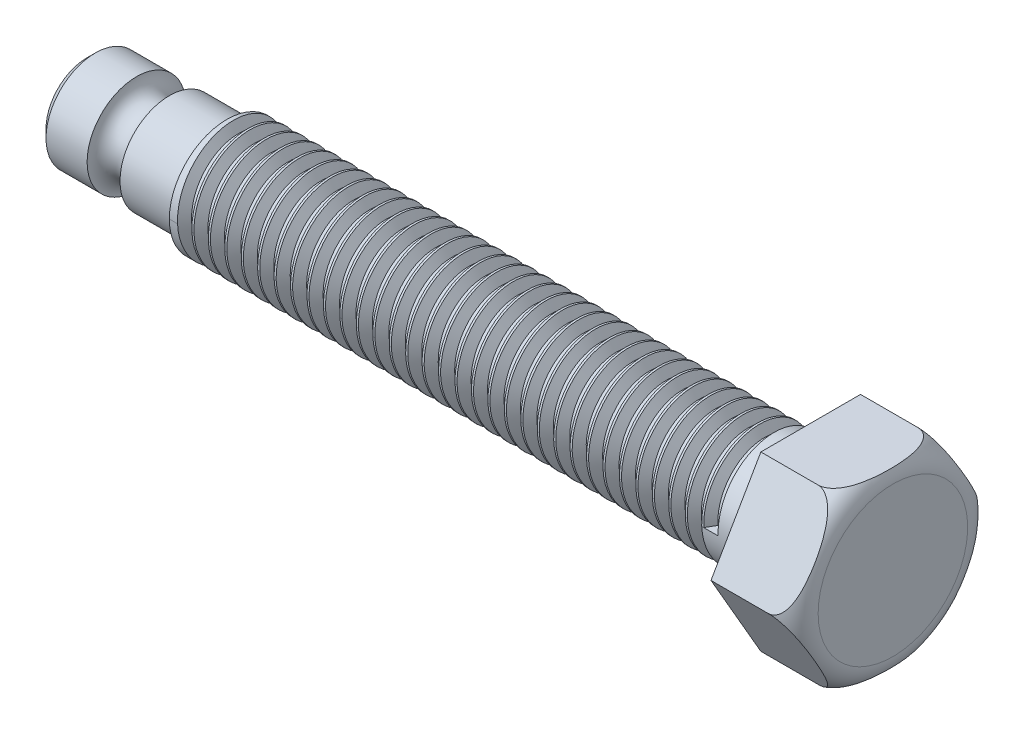
SolidWorks part; units mm, degrees
ref_plane "Front Plane" through (0, 0, 0) normal (0, 0, 1) x (1, 0, 0)
ref_plane "Top Plane" through (0, 0, 0) normal (0, 1, 0) x (1, 0, 0)
ref_plane "Right Plane" through (0, 0, 0) normal (1, 0, 0) x (0, 0, -1)
sketch "Esquisse1" plane through (0, 0, 0) normal (0, 0, 1) x (1, 0, 0)
  line L0 (-21.5385, 0) -> (27.7846, 0) construction
  line L1 (0, 21) -> (0, -25.0923) construction
  line L2 (0, 0) -> (0, 6)
  line L3 (0, 6) -> (6, 6)
  line L4 (88, 6) -> (88, 14)
  line L5 (88, 14) -> (98, 14)
  line L6 (98, 14) -> (98, 0)
  line L7 (98, 0) -> (0, 0)
  line L8 (10, 6) -> (17, 6)
  line L9 (17, 6) -> (17, 7)
  line L10 (17, 7) -> (88, 7)
  arc A0 (6, 6) -> (10, 6) centre (8, 6) ccw
  dimension "D3" = 2
  dimension "D1" = 6
  dimension "D2" = 8
  dimension "D4" = 10
  dimension "D5" = 14
  dimension "D6" = 80
  dimension "D7" = 17
  dimension "D8" = 1
revolve "Révolution2" add sketch "Esquisse1" angle 360 about L0 region at (54.4948, 4.085, 0)
sketch "Esquisse7" plane through (98, 0, 0) normal (1, 0, 0) x (0, 0, -1)
  line L0 (0, 0) -> (12.1244, 0)
  line L1 (0, 0) -> (6.0622, -10.5)
  line L2 (0, 0) -> (-6.0622, -10.5)
  line L3 (0, 0) -> (-12.1244, 0)
  line L4 (0, 0) -> (-6.0622, 10.5)
  line L5 (0, 0) -> (6.0622, 10.5)
  line L6 (12.1244, 0) -> (6.0622, 10.5)
  line L8 (-6.0622, 10.5) -> (6.0622, 10.5)
  line L10 (-6.0622, 10.5) -> (-12.1244, 0)
  line L12 (-12.1244, 0) -> (-6.0622, -10.5)
  line L13 (6.0622, -10.5) -> (-6.0622, -10.5)
  line L14 (12.1244, 0) -> (6.0622, -10.5)
  point P2 (-9.0933, -5.25)
  point P10 (0, 0)
  circle M8 centre (0, 0) radius 14
  dimension "D1" = 10.5
  dimension "D2" = 6
extrude "Enlèv. mat.-Extru.2" cut sketch "Esquisse7" against normal blind 10 contours L6 L14 L13 L12 L10 L8 M8 region at (98, 0, 13.604)
ref_plane "Plan3" through (0, 0, 0) normal (0, 1, 0) x (1, 0, 0)
sketch "Esquisse11" plane through (0, 0, 0) normal (0, 1, 0) x (1, 0, 0)
  line L1 (98, 12.1244) -> (94.9689, 12.1244)
  line L2 (88, 12.1244) -> (98, 12.1244) construction
  line L3 (98, 12.1244) -> (98, 9.0933)
  line L4 (-2.5079, 0) -> (34.4449, 0) construction
  line L5 (98, 12.1244) -> (98, 6.0622) construction
  arc A1 (98, 9.0933) -> (94.9689, 12.1244) centre (94.9689, 9.0933) ccw
revolve "Enlèvement de matière-Révolution4" cut sketch "Esquisse11" angle 360 about L4
thread "Filetage2" pitch 2 method cut profile "Profil de filetage3" start angle 0, offset 0, length 65, pitch 2, diameter 14
ref_plane "Plan4" through (17, 0, -7) normal (0, -1, 0) x (0, 0, -1)
sketch "Profil de filetage3" plane through (17, 0, -7) normal (0, -1, 0) x (0, 0, -1)
  line L0 (0, 0) -> (0, 2) construction
  line L11 (0, 0) -> (0, 1.75)
  line L12 (0, 1.75) -> (-1.0825, 1.125)
  line L13 (-1.0825, 1.125) -> (-1.0825, 0.625)
  line L15 (-1.0825, 0.625) -> (0, 0)
  line L17 (-1.0825, 0.875) -> (0, 0.875) construction
  point P2 (0, 0)
  dimension "Pitch" = 2
  dimension "Profile_Angle" = 60
  dimension "Profile_Land" = 0.5
  dimension "Profile_Height" = 1.0825
chamfer "Chanfrein3" distance 1 angle 45 1 edges at (0, 0, 6)
